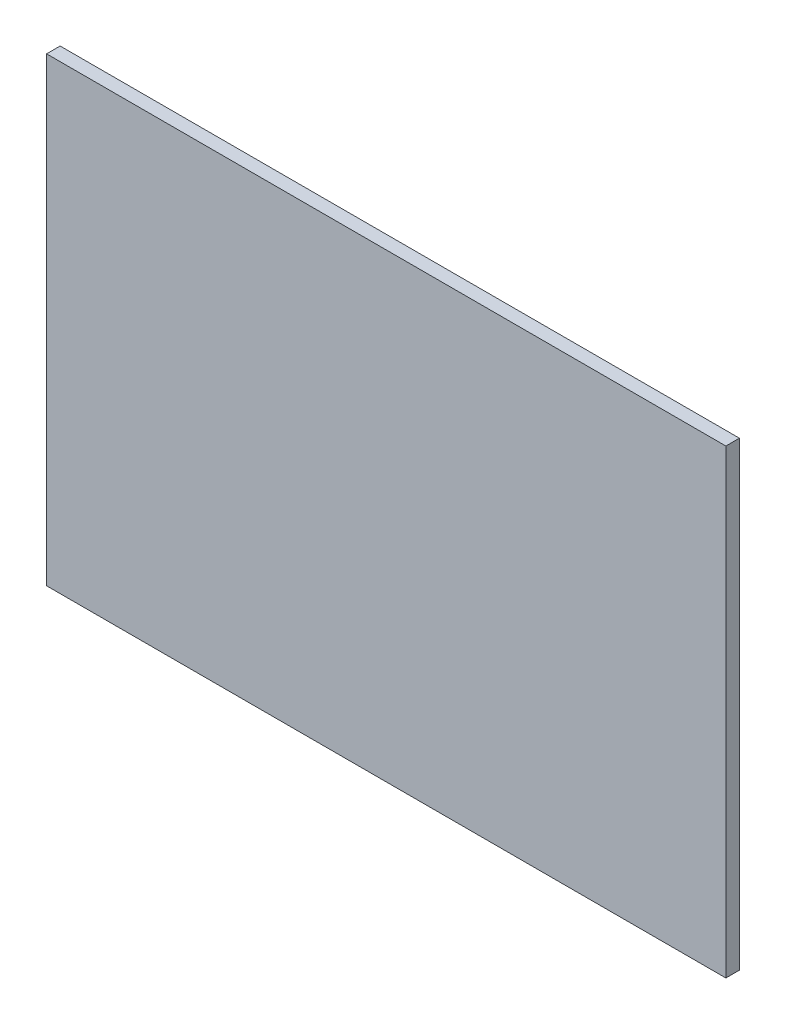
SolidWorks part; units mm, degrees
ref_plane "Front Plane" through (0, 0, 0) normal (0, 0, 1) x (1, 0, 0)
ref_plane "Top Plane" through (0, 0, 0) normal (0, 1, 0) x (1, 0, 0)
ref_plane "Right Plane" through (0, 0, 0) normal (1, 0, 0) x (0, 0, -1)
sketch "Sketch1" plane through (0, 0, 0) normal (0, 0, 1) x (1, 0, 0)
  line L1 (0, 0) -> (-159.1564, 0)
  line L2 (0, 0) -> (0, 107.95)
  line L3 (0, 107.95) -> (-159.1564, 107.95)
  line L4 (-159.1564, 0) -> (-159.1564, 107.95)
  dimension "D1" = 107.95
  dimension "D2" = 159.1564
extrude "Boss-Extrude1" add sketch "Sketch1" along normal blind 3.175
